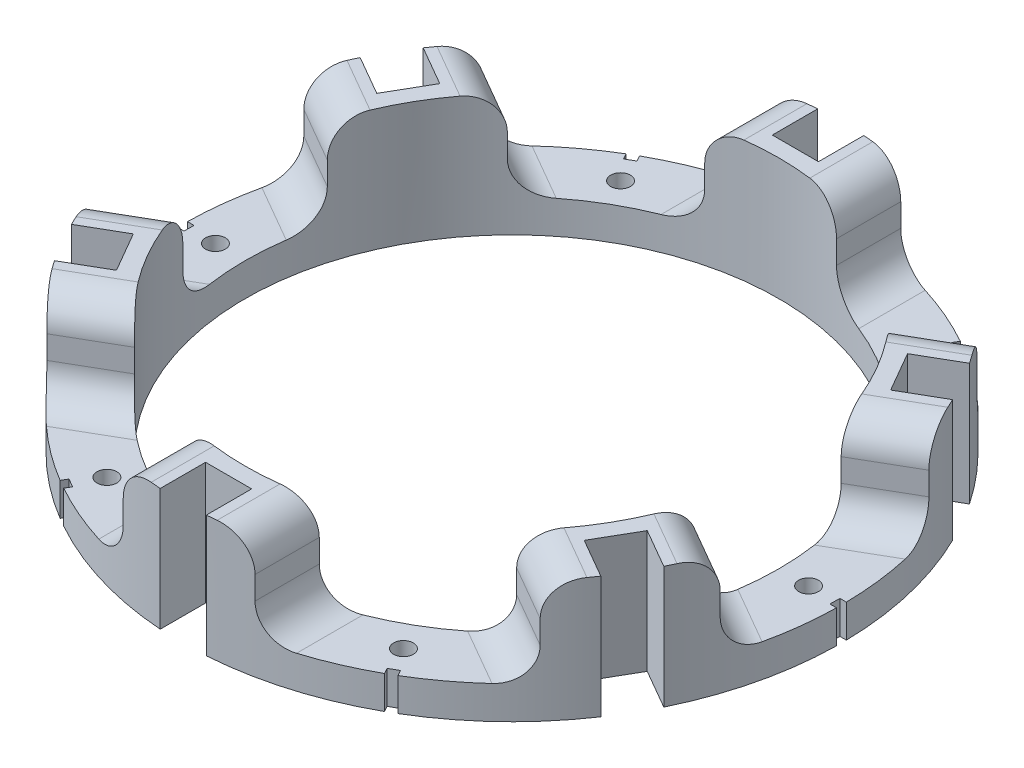
SolidWorks part; units mm, degrees
ref_plane "Спереди" through (0, 0, 0) normal (0, 0, 1) x (1, 0, 0)
ref_plane "Сверху" through (0, 0, 0) normal (0, 1, 0) x (1, 0, 0)
ref_plane "Справа" through (0, 0, 0) normal (1, 0, 0) x (0, 0, -1)
sketch "Эскиз1" plane through (0, 0, 0) normal (0, 1, 0) x (1, 0, 0)
  circle A0 centre (0, 0) radius 81
  circle A1 centre (0, 0) radius 100
  dimension "D1" = 200
  dimension "D2" = 162
extrude "Бобышка-Вытянуть1" add sketch "Эскиз1" along normal blind 10
sketch "Эскиз2" plane through (0, 10, 0) normal (0, 1, 0) x (1, 0, 0)
  line L0 (0, 0) -> (0, 93) construction
  line L1 (-7, 100) -> (7, 100)
  line L2 (-7, 100) -> (-7, 86)
  line L3 (-7, 86) -> (7, 86)
  line L4 (7, 100) -> (7, 86)
  line L5 (-7, 100) -> (7, 86) construction
  line L6 (-7, 86) -> (7, 100) construction
  circle A0 centre (0, 0) radius 100 construction
  point P0 (0, 93)
  dimension "D1" = 14
  dimension "D2" = 14
ref_plane "Плоскость1" through (0, 0, -100) normal (0, 0, -1) x (-1, 0, 0)
sketch "Эскиз5" plane through (0, 10, 0) normal (0, 1, 0) x (1, 0, 0)
  line L0 (-20, 78.492) -> (-20, 97.9796)
  line L1 (20, 78.492) -> (20, 97.9796)
  line L3 (0, 93) -> (-20, 93) construction
  line L4 (-7, 100) -> (7, 86) construction
  line L5 (0, 93) -> (20, 93) construction
  arc A0 (-20, 78.492) -> (20, 78.492) centre (0, 0) cw
  circle A1 centre (0, 0) radius 81 construction
  arc A2 (-20, 97.9796) -> (20, 97.9796) centre (0, 0) cw
  circle A3 centre (0, 0) radius 100 construction
  dimension "D1" = 40
extrude "Бобышка-Вытянуть2" add sketch "Эскиз5" along normal blind 27
extrude "Вырез-Вытянуть2" cut sketch "Эскиз2" along normal through all and the other way through all contours L3 L4 L1 L2
fillet "Скругление1" radius 10 4 edges at (-20, 10, -88.2358) (-20, 37, -88.2358) (20, 10, -88.2358) (20, 37, -88.2358)
pattern_circular "Круговой массив2" count 6 over 360 about axis through (0, 10, 0) along (0, 1, 0) of "Скругление1", "Вырез-Вытянуть2", "Бобышка-Вытянуть2"
sketch "Эскиз6" plane through (0, 10, 0) normal (0, 1, 0) x (1, 0, 0)
  line L0 (0, 0) -> (-45, 77.9423) construction
  line L1 (0, 0) -> (0, 93) construction
  line L2 (-45, 77.9423) -> (-49.0057, 84.8804) construction
  line L3 (-50.3161, 84.1504) -> (-47.6954, 85.6105)
  line L4 (-51.2895, 85.8976) -> (-48.6688, 87.3576)
  line L5 (-50.3161, 84.1504) -> (-51.2895, 85.8976)
  line L6 (-47.6954, 85.6105) -> (-48.6688, 87.3576)
  circle A0 centre (0, 0) radius 90 construction
  circle A1 centre (-45, 77.9423) radius 3
  arc A2 (-30, 95.3939) -> (-67.6136, 73.6777) centre (0, 0) ccw construction
  point P14 (-49.0057, 84.8804)
  point P17 (-49.9791, 86.6276)
  dimension "D1" = 180
  dimension "D3" = 6
  dimension "D2" = 30
  dimension "D4" = 3
  dimension "D5" = 2
extrude "Вырез-Вытянуть3" cut sketch "Эскиз6" against normal through all
pattern_circular "Круговой массив3" count 6 over 360 about axis through (0, 10, 0) along (0, 1, 0) of "Вырез-Вытянуть3"
